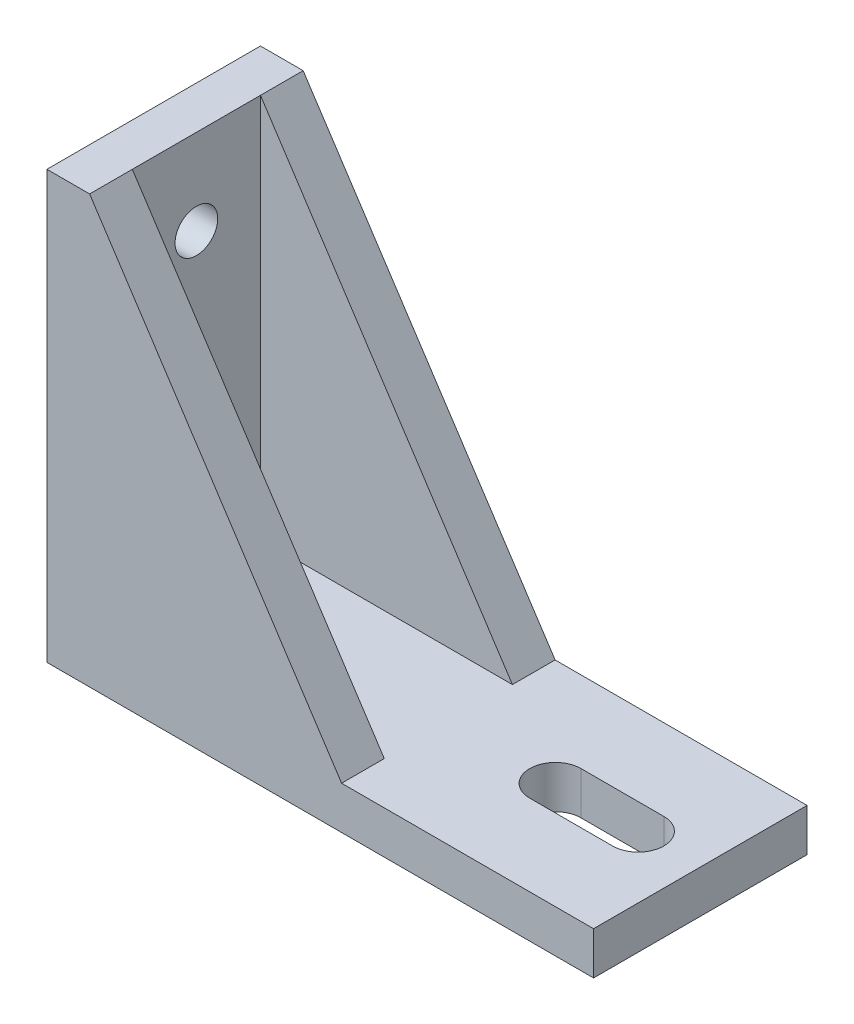
SolidWorks part; units mm, degrees
ref_plane "Front Plane" through (0, 0, 0) normal (0, 0, 1) x (1, 0, 0)
ref_plane "Top Plane" through (0, 0, 0) normal (0, 1, 0) x (1, 0, 0)
ref_plane "Right Plane" through (0, 0, 0) normal (1, 0, 0) x (0, 0, -1)
sketch "Sketch1" plane through (0, 0, 0) normal (0, 1, 0) x (1, 0, 0)
  line L1 (-30.1722, 4.0464) -> (33.8278, 4.0464)
  line L2 (-30.1722, 4.0464) -> (-30.1722, -10.9536)
  line L3 (-30.1722, -10.9536) -> (33.8278, -10.9536)
  line L4 (33.8278, 4.0464) -> (33.8278, -10.9536)
  dimension "D1" = 15
  dimension "D2" = 64
extrude "Boss-Extrude1" add sketch "Sketch1" along normal blind 5
sketch "Sketch3" plane through (0, 5, 0) normal (0, 1, 0) x (1, 0, 0)
  line L0 (-30.1722, 4.0464) -> (-25.1722, 4.0464)
  line L1 (33.8278, 4.0464) -> (-30.1722, 4.0464) construction
  line L2 (-30.1722, -10.9536) -> (-25.1722, -10.9536)
  line L3 (-30.1722, -10.9536) -> (33.8278, -10.9536) construction
  line L4 (-25.1722, 4.0464) -> (-25.1722, -10.9536)
  line L5 (-30.1722, 4.0464) -> (-30.1722, -10.9536)
extrude "Boss-Extrude2" add sketch "Sketch3" along normal blind 45
sketch "Sketch4" plane through (-30.1722, 0, 0) normal (-1, 0, 0) x (0, 0, 1)
  line L0 (3.4536, 0) -> (3.4536, 50)
  line L2 (-4.0464, 0) -> (10.9536, 0) construction
  line L3 (3.4536, 0) -> (3.4536, 15)
  line L4 (3.4536, 50) -> (3.4536, 40)
hole_wizard "Ø5.0mm Dowel Hole1" positions "Sketch5" profile "Sketch6" hole size "Ø5.0" standard "ANSI Metric" end condition up to next
sketch "Sketch5" plane through (-30.1722, 0, 0) normal (-1, 0, 0) x (0, 0, 1)
  point P3 (3.4536, 15)
  point P7 (3.4536, 40)
sketch "Sketch6" plane through (-30.1722, 15, 3.4536) normal (0, 1, 0) x (0, 0, 1)
  line L0 (0, 0) -> (0, 5)
  line L1 (0, 5) -> (2.5, 5)
  line L2 (2.5, 5) -> (2.5, 0)
  line L5 (2.5, 0) -> (0, 0)
  line L11 (0, -6.35) -> (0, 107.95) construction
  dimension "Thru Hole Dia." = 5
  dimension "Thru Hole Depth" = 5
sketch "Sketch7" plane through (0, 0, 0) normal (0, -1, 0) x (1, 0, 0)
  line L0 (-30.1722, 3.4536) -> (33.8278, 3.4536)
  line L1 (-30.1722, -4.0464) -> (-30.1722, 10.9536) construction
  line L2 (33.8278, 10.9536) -> (33.8278, -4.0464) construction
hole_wizard "Ø6.0mm Dowel Slot1" positions "Sketch8" profile "Sketch9" size "Ø6.0" standard "ANSI Metric" slot yes end condition up to next
sketch "Sketch8" plane through (0, 5, 0) normal (0, 1, 0) x (1, 0, 0)
  line L0 (13.8542, -3.4536) -> (29.5542, -3.4537) construction
  point P0 (21.7042, -3.4537)
  dimension "D1" = 15.7
sketch "Sketch9" plane through (21.7042, 5, 3.4537) normal (1, 0, 0) x (0, 0, 1)
  line L0 (0, 0) -> (0, 5)
  line L1 (0, 5) -> (3, 5)
  line L2 (3, 5) -> (3, 0)
  line L5 (3, 0) -> (0, 0)
  line L11 (0, -6.35) -> (0, 107.95) construction
  dimension "Thru Hole Dia." = 6
  dimension "Thru Hole Depth" = 5
sketch "Sketch10" plane through (0, 0, 10.9536) normal (0, 0, 1) x (1, 0, 0)
  line L0 (-25.1722, 50) -> (4.3278, 5)
  line L1 (-25.1722, 5) -> (33.8278, 5) construction
  line L2 (4.3278, 5) -> (33.8278, 5)
  line L3 (33.8278, 5) -> (33.8278, 0)
  line L4 (33.8278, 0) -> (-30.1722, 0)
  line L5 (-30.1722, 0) -> (-30.1722, 50)
  line L6 (-30.1722, 50) -> (-25.1722, 50)
extrude "Boss-Extrude3" add sketch "Sketch10" along normal blind 5
sketch "Sketch11" plane through (0, 0, -4.0464) normal (0, 0, -1) x (-1, 0, 0)
  line L0 (25.1722, 50) -> (30.1722, 50)
  line L1 (30.1722, 50) -> (30.1722, 0)
  line L2 (30.1722, 0) -> (-33.8278, 0)
  line L3 (-33.8278, 0) -> (-33.8278, 5)
  line L4 (-33.8278, 5) -> (-4.3278, 5)
  line L5 (-33.8278, 5) -> (25.1722, 5) construction
  line L6 (-4.3278, 5) -> (25.1722, 50)
extrude "Boss-Extrude4" add sketch "Sketch11" along normal blind 5
